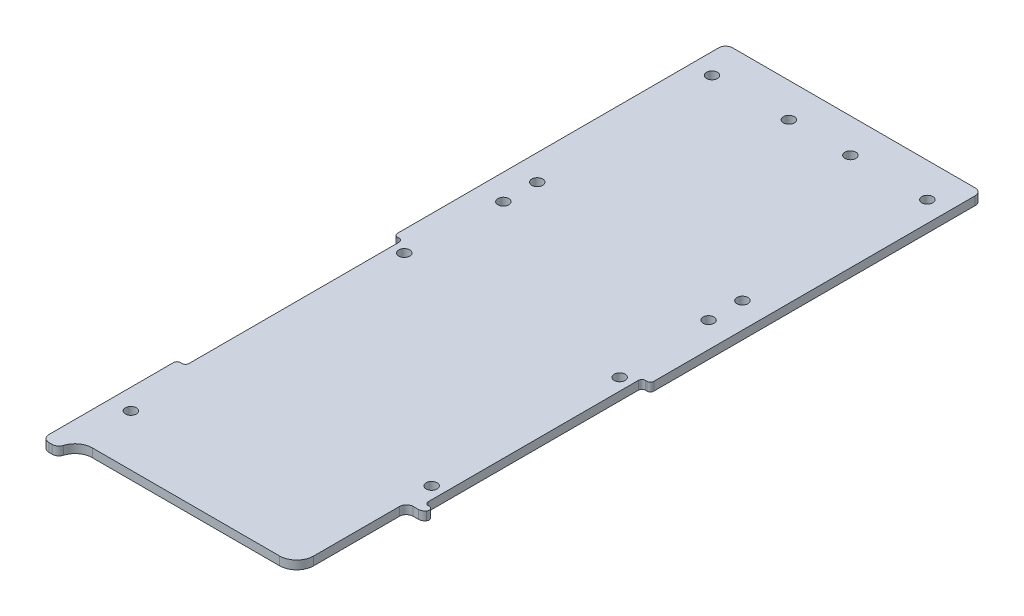
SolidWorks part; units mm, degrees
ref_plane "Front Plane" through (0, 0, 0) normal (0, 0, 1) x (1, 0, 0)
ref_plane "Top Plane" through (0, 0, 0) normal (0, 1, 0) x (1, 0, 0)
ref_plane "Right Plane" through (0, 0, 0) normal (1, 0, 0) x (0, 0, -1)
sketch "Sketch1" plane through (0, 0, 0) normal (0, 1, 0) x (1, 0, 0)
  line L0 (-39.9997, 0) -> (-39.9997, 114.3) construction
  line L1 (-47.625, 127) -> (47.625, 127)
  line L2 (-47.625, 127) -> (-47.625, -127)
  line L3 (-47.625, -127) -> (47.625, -127)
  line L4 (47.625, 127) -> (47.625, -127)
  line L5 (-47.625, 127) -> (47.625, -127) construction
  line L6 (-47.625, -127) -> (47.625, 127) construction
  line L7 (0, 0) -> (0, 127) construction
  line L8 (-39.9997, 0) -> (-39.9997, -101.6) construction
  line L9 (-39.9997, 0) -> (0, 0) construction
  line L10 (-41.275, -127) -> (-41.275, -120.65)
  line L11 (-41.275, -120.65) -> (41.275, -120.65)
  line L12 (41.275, -120.65) -> (41.275, -127)
  line L13 (-39.9997, 114.3) -> (-11.4247, 114.3) construction
  line L14 (39.9997, 114.3) -> (11.4247, 114.3) construction
  circle A0 centre (-39.9997, 114.3) radius 2.032
  circle A1 centre (-39.9997, 0) radius 2.032
  circle A2 centre (-39.9997, -101.6) radius 2.032
  circle A3 centre (39.9997, -101.6) radius 2.032
  circle A4 centre (39.9997, 0) radius 2.032
  circle A5 centre (39.9997, 114.3) radius 2.032
  circle A6 centre (-11.4247, 114.3) radius 2.032
  circle A7 centre (11.4247, 114.3) radius 2.032
  circle A8 centre (-39.9997, -69.85) radius 2.032
  circle A9 centre (39.9997, -69.85) radius 2.032
  point P0 (0, 0)
  dimension "D4" = 4.064
  dimension "D10" = 28.575
  dimension "D1" = 95.25
  dimension "D2" = 254
  dimension "D3" = 7.6253
  dimension "D5" = 12.7
  dimension "D6" = 25.4
  dimension "D7" = 6.35
  dimension "D8" = 6.35
  dimension "D9" = 6.35
  dimension "D11" = 69.85
extrude "Boss-Extrude1" add sketch "Sketch1" along normal blind 3.175 contours L4 L1 L2 L3 A4 A0 A1 A2 A3 A5 | A8 | A3 region at (0, 0, -2.6944) region at (39.9997, 0, 101.6) region at (-39.9997, 0, 69.85)
fillet "Fillet1" radius 2.54 4 edges at (-47.625, 1.5875, -127) (47.625, 1.5875, -127) (47.625, 1.5875, 127) (-47.625, 1.5875, 127)
fillet "Fillet2" radius 2.54 2 edges at (41.275, 1.5875, 127) (-41.275, 1.5875, 127)
fillet "Fillet3" radius 6.35 2 edges at (41.275, 1.5875, 120.65) (-41.275, 1.5875, 120.65)
sketch "Sketch2" plane through (0, 0, 0) normal (0, -1, 0) x (1, 0, 0)
  line L1 (43.815, 127) -> (45.085, 127) construction
  line L2 (40.6451, 123.5787) -> (40.6451, 79.8881)
  line L3 (40.6451, 79.8881) -> (47.625, 79.8881)
  line L11 (47.625, -124.46) -> (47.625, 124.46) construction
  line L12 (43.815, 127) -> (45.085, 127)
  line L13 (47.625, 79.8881) -> (47.625, 124.46)
  arc A0 (35.2956, 120.65) -> (41.3809, 125.1857) centre (35.2956, 127) ccw construction
  arc A1 (43.815, 127) -> (41.3809, 125.1857) centre (43.815, 124.46) ccw construction
  arc A2 (47.625, 124.46) -> (45.085, 127) centre (45.085, 124.46) ccw construction
  arc A3 (40.6451, 123.5787) -> (41.3809, 125.1857) centre (35.2956, 127) ccw
  arc A4 (43.815, 127) -> (41.3809, 125.1857) centre (43.815, 124.46) ccw
  arc A5 (47.625, 124.46) -> (45.085, 127) centre (45.085, 124.46) ccw
  dimension "D2" = 47.1119
  dimension "D1" = 6.9799
extrude "Cut-Extrude1" cut sketch "Sketch2" against normal through all
fillet "Fillet4" radius 6.35 1 edges at (40.6451, 1.5875, 123.5787)
fillet "Fillet5" radius 2.54 2 edges at (47.625, 1.5875, 79.8881) (40.6451, 1.5875, 79.8881)
sketch "Sketch3" plane through (0, 0, 0) normal (0, -1, 0) x (1, 0, 0)
  line L0 (-36.3063, -49.7791) -> (-39.9131, -49.7791) construction
  line L1 (-40.4211, -49.276) -> (-40.4211, -45.7043) construction
  line L2 (-35.7983, -45.7043) -> (-35.7983, -49.276) construction
  line L3 (-39.9131, -45.2013) -> (-36.3063, -45.2013) construction
  line L4 (-36.3063, -37.2027) -> (-39.9131, -37.2027) construction
  line L5 (-35.7983, -33.1279) -> (-35.7983, -36.6996) construction
  line L6 (-40.4211, -36.6996) -> (-40.4211, -33.1279) construction
  line L7 (-39.9131, -32.6249) -> (-36.3063, -32.6249) construction
  line L8 (36.2869, -32.6249) -> (39.8937, -32.6249) construction
  line L9 (40.4017, -33.1279) -> (40.4017, -36.6996) construction
  line L10 (39.8937, -37.2027) -> (36.2869, -37.2027) construction
  line L11 (35.7789, -36.6996) -> (35.7789, -33.1279) construction
  line L12 (36.2869, -45.2013) -> (39.8937, -45.2013) construction
  line L13 (35.7789, -49.276) -> (35.7789, -45.7043) construction
  line L14 (40.4017, -45.7043) -> (40.4017, -49.276) construction
  line L15 (39.8937, -49.7791) -> (36.2869, -49.7791) construction
  line L16 (-36.3063, -49.7791) -> (-39.9131, -49.7791)
  line L17 (-40.4211, -49.276) -> (-40.4211, -45.7043)
  line L18 (-35.7983, -45.7043) -> (-35.7983, -49.276)
  line L19 (-39.9131, -45.2013) -> (-36.3063, -45.2013)
  line L20 (-36.3063, -37.2027) -> (-39.9131, -37.2027)
  line L21 (-35.7983, -33.1279) -> (-35.7983, -36.6996)
  line L22 (-40.4211, -36.6996) -> (-40.4211, -33.1279)
  line L23 (-39.9131, -32.6249) -> (-36.3063, -32.6249)
  line L24 (36.2869, -32.6249) -> (39.8937, -32.6249)
  line L25 (40.4017, -33.1279) -> (40.4017, -36.6996)
  line L26 (39.8937, -37.2027) -> (36.2869, -37.2027)
  line L27 (35.7789, -36.6996) -> (35.7789, -33.1279)
  line L28 (36.2869, -45.2013) -> (39.8937, -45.2013)
  line L29 (35.7789, -49.276) -> (35.7789, -45.7043)
  line L30 (40.4017, -45.7043) -> (40.4017, -49.276)
  line L31 (39.8937, -49.7791) -> (36.2869, -49.7791)
  line L32 (-47.625, -25.836) -> (47.625, -25.836)
  line L33 (-47.625, -124.46) -> (-47.625, 124.46) construction
  line L34 (47.625, -124.46) -> (47.625, 77.3481) construction
  line L35 (0, -25.836) -> (0, -56.0686) construction
  line L1362 (-40.4211, -34.9138) -> (-35.7983, -34.9138)
  line L1857 (-38.1097, -32.6249) -> (-38.1097, -37.2027)
  line L1858 (-38.1097, -45.2013) -> (-38.1097, -49.7791)
  line L1859 (-40.4211, -47.4902) -> (-35.7983, -47.4902)
  circle A0 centre (-38.1097, -34.9138) radius 2.032
  circle A1 centre (-38.1097, -47.4902) radius 2.032
  circle A2 centre (38.1097, -47.4902) radius 2.032
  circle A3 centre (38.1097, -34.9138) radius 2.032
  ellipse E0 centre (-39.9131, -45.7043) end of major axis (-39.4051, -45.7043) minor radius 0.5031 (-39.9131, -45.2013) -> (-40.4211, -45.7043) ccw construction
  ellipse E1 centre (-39.9131, -49.276) end of major axis (-39.4051, -49.276) minor radius 0.5031 (-40.4211, -49.276) -> (-39.9131, -49.7791) ccw construction
  ellipse E6 centre (-36.3063, -49.276) end of major axis (-35.7983, -49.276) minor radius 0.5031 (-36.3063, -49.7791) -> (-35.7983, -49.276) ccw construction
  ellipse E7 centre (-36.3063, -45.7043) end of major axis (-35.7983, -45.7043) minor radius 0.5031 (-35.7983, -45.7043) -> (-36.3063, -45.2013) ccw construction
  ellipse E8 centre (-39.9131, -36.6996) end of major axis (-39.4051, -36.6996) minor radius 0.5031 (-40.4211, -36.6996) -> (-39.9131, -37.2027) ccw construction
  ellipse E9 centre (-36.3063, -36.6996) end of major axis (-35.7983, -36.6996) minor radius 0.5031 (-36.3063, -37.2027) -> (-35.7983, -36.6996) ccw construction
  ellipse E10 centre (-36.3063, -33.1279) end of major axis (-35.7983, -33.1279) minor radius 0.5031 (-35.7983, -33.1279) -> (-36.3063, -32.6249) ccw construction
  ellipse E11 centre (-39.9131, -33.1279) end of major axis (-39.4051, -33.1279) minor radius 0.5031 (-39.9131, -32.6249) -> (-40.4211, -33.1279) ccw construction
  ellipse E12 centre (39.8937, -33.1279) end of major axis (40.4017, -33.1279) minor radius 0.5031 (40.4017, -33.1279) -> (39.8937, -32.6249) ccw construction
  ellipse E13 centre (36.2869, -33.1279) end of major axis (36.7949, -33.1279) minor radius 0.5031 (36.2869, -32.6249) -> (35.7789, -33.1279) ccw construction
  ellipse E14 centre (39.8937, -36.6996) end of major axis (40.4017, -36.6996) minor radius 0.5031 (39.8937, -37.2027) -> (40.4017, -36.6996) ccw construction
  ellipse E15 centre (36.2869, -36.6996) end of major axis (36.7949, -36.6996) minor radius 0.5031 (35.7789, -36.6996) -> (36.2869, -37.2027) ccw construction
  ellipse E16 centre (36.2869, -45.7043) end of major axis (36.7949, -45.7043) minor radius 0.5031 (36.2869, -45.2013) -> (35.7789, -45.7043) ccw construction
  ellipse E17 centre (36.2869, -49.276) end of major axis (36.7949, -49.276) minor radius 0.5031 (35.7789, -49.276) -> (36.2869, -49.7791) ccw construction
  ellipse E18 centre (39.8937, -45.7043) end of major axis (40.4017, -45.7043) minor radius 0.5031 (40.4017, -45.7043) -> (39.8937, -45.2013) ccw construction
  ellipse E19 centre (39.8937, -49.276) end of major axis (40.4017, -49.276) minor radius 0.5031 (39.8937, -49.7791) -> (40.4017, -49.276) ccw construction
  ellipse E20 centre (-39.9131, -45.7043) end of major axis (-39.4051, -45.7043) minor radius 0.5031 (-39.9131, -45.2013) -> (-40.4211, -45.7043) ccw
  ellipse E21 centre (-39.9131, -49.276) end of major axis (-39.4051, -49.276) minor radius 0.5031 (-40.4211, -49.276) -> (-39.9131, -49.7791) ccw
  ellipse E22 centre (-36.3063, -49.276) end of major axis (-35.7983, -49.276) minor radius 0.5031 (-36.3063, -49.7791) -> (-35.7983, -49.276) ccw
  ellipse E23 centre (-36.3063, -45.7043) end of major axis (-35.7983, -45.7043) minor radius 0.5031 (-35.7983, -45.7043) -> (-36.3063, -45.2013) ccw
  ellipse E24 centre (-39.9131, -36.6996) end of major axis (-39.4051, -36.6996) minor radius 0.5031 (-40.4211, -36.6996) -> (-39.9131, -37.2027) ccw
  ellipse E25 centre (-36.3063, -36.6996) end of major axis (-35.7983, -36.6996) minor radius 0.5031 (-36.3063, -37.2027) -> (-35.7983, -36.6996) ccw
  ellipse E26 centre (-36.3063, -33.1279) end of major axis (-35.7983, -33.1279) minor radius 0.5031 (-35.7983, -33.1279) -> (-36.3063, -32.6249) ccw
  ellipse E27 centre (-39.9131, -33.1279) end of major axis (-39.4051, -33.1279) minor radius 0.5031 (-39.9131, -32.6249) -> (-40.4211, -33.1279) ccw
  ellipse E28 centre (39.8937, -33.1279) end of major axis (40.4017, -33.1279) minor radius 0.5031 (40.4017, -33.1279) -> (39.8937, -32.6249) ccw
  ellipse E29 centre (36.2869, -33.1279) end of major axis (36.7949, -33.1279) minor radius 0.5031 (36.2869, -32.6249) -> (35.7789, -33.1279) ccw
  ellipse E30 centre (39.8937, -36.6996) end of major axis (40.4017, -36.6996) minor radius 0.5031 (39.8937, -37.2027) -> (40.4017, -36.6996) ccw
  ellipse E31 centre (36.2869, -36.6996) end of major axis (36.7949, -36.6996) minor radius 0.5031 (35.7789, -36.6996) -> (36.2869, -37.2027) ccw
  ellipse E32 centre (36.2869, -45.7043) end of major axis (36.7949, -45.7043) minor radius 0.5031 (36.2869, -45.2013) -> (35.7789, -45.7043) ccw
  ellipse E33 centre (36.2869, -49.276) end of major axis (36.7949, -49.276) minor radius 0.5031 (35.7789, -49.276) -> (36.2869, -49.7791) ccw
  ellipse E34 centre (39.8937, -45.7043) end of major axis (40.4017, -45.7043) minor radius 0.5031 (40.4017, -45.7043) -> (39.8937, -45.2013) ccw
  ellipse E35 centre (39.8937, -49.276) end of major axis (40.4017, -49.276) minor radius 0.5031 (39.8937, -49.7791) -> (40.4017, -49.276) ccw
  dimension "D2" = 4.064
extrude "Cut-Extrude2" cut sketch "Sketch3" against normal through all contours A0 | A1 | A2 | A3
sketch "Sketch4" plane through (0, 3.175, 0) normal (0, 1, 0) x (1, 0, 0)
  line L11 (-47.625, 124.46) -> (-47.625, -124.46) construction
  line L12 (-47.625, -76.835) -> (-44.45, -76.835)
  line L13 (-47.625, -76.835) -> (-47.625, 3.81)
  line L15 (-47.625, 3.81) -> (-44.45, 3.81)
  line L16 (-44.45, -76.835) -> (-44.45, 3.81)
  line L17 (47.625, 124.46) -> (47.625, -77.3481) construction
  line L18 (47.625, -76.835) -> (44.45, -76.835)
  line L19 (47.625, -76.835) -> (47.625, 3.81)
  line L20 (47.625, 3.81) -> (44.45, 3.81)
  line L45 (44.45, -76.835) -> (44.45, 3.81)
  line L47 (43.1851, -79.8881) -> (45.085, -79.8881) construction
  dimension "D1" = 3.175
  dimension "D2" = 80.645
  dimension "D3" = 3.0531
extrude "Cut-Extrude3" cut sketch "Sketch4" against normal through all and the other way through all
fillet "Fillet6" radius 1.27 8 edges at (-44.45, 1.5875, -3.81) (-47.625, 1.5875, -3.81) (-47.625, 1.5875, 76.835) (-44.45, 1.5875, 76.835) (44.45, 1.5875, 76.835) (47.625, 1.5875, 76.835) (44.45, 1.5875, -3.81) (47.625, 1.5875, -3.81)
